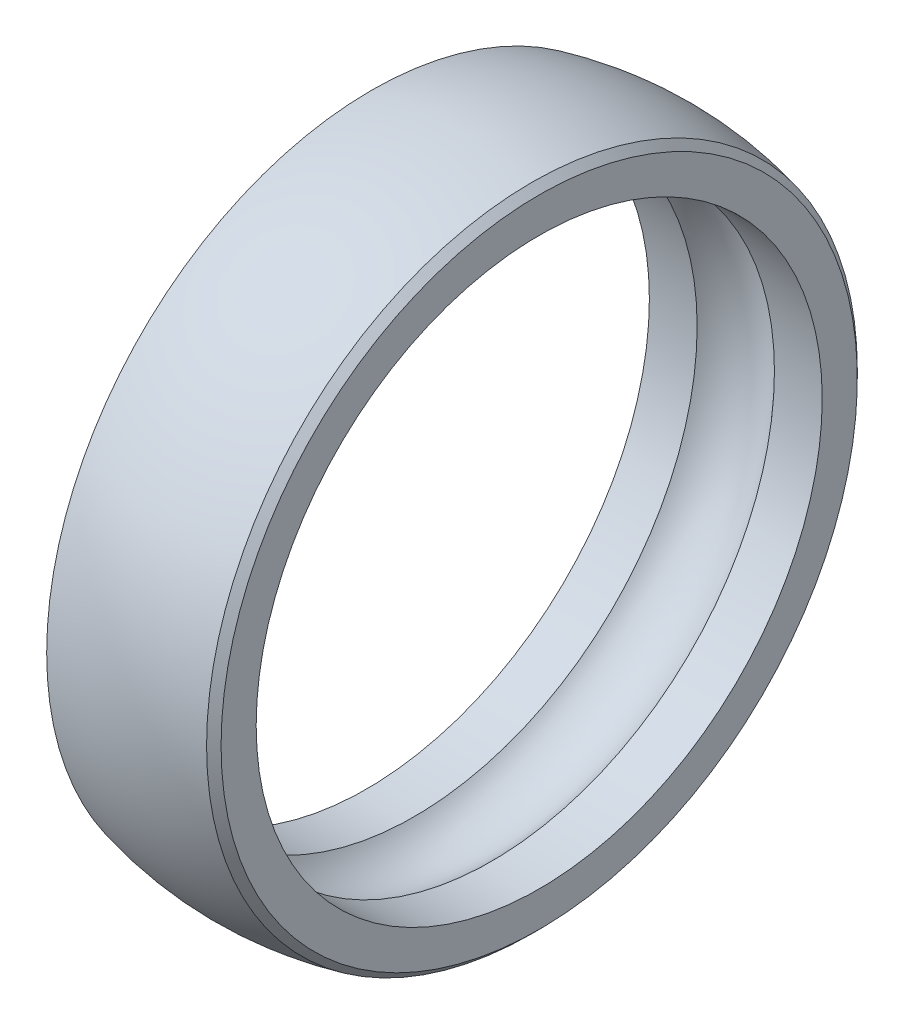
SolidWorks part; units mm, degrees
ref_plane "Plan1" through (0, 0, 0) normal (0, 0, 1) x (1, 0, 0)
ref_plane "Plan2" through (0, 0, 0) normal (0, 1, 0) x (1, 0, 0)
ref_plane "Plan3" through (0, 0, 0) normal (1, 0, 0) x (0, 0, -1)
ref_axis "Axe1" through (-50, 0, 0) along (1, 0, 0)
sketch "Esquisse1" plane through (0, 0, 0) normal (0, 1, 0) x (1, 0, 0)
  line L0 (0, 30) -> (0, 16) construction
  line L1 (16, 26.2) -> (0, 26.2) construction
  line L2 (16, 30) -> (16, 16) construction
  line L3 (1, 31) -> (15, 31) construction
  line L4 (0, 30) -> (0, 26.2)
  line L5 (16, 26.2) -> (11.5777, 26.2)
  line L6 (0, 0) -> (12, 0) construction
  line L7 (-50, 0) -> (200, 0) construction
  line L8 (16, 30) -> (16, 26.2)
  line L9 (1, 31) -> (15, 31)
  line L10 (4.4223, 26.2) -> (0, 26.2)
  arc A0 (1, 31) -> (0, 30) centre (1, 30) ccw construction
  circle A1 centre (8, 23) radius 4.8 construction
  arc A3 (16, 30) -> (15, 31) centre (15, 30) ccw construction
  arc A4 (1, 31) -> (0, 30) centre (1, 30) ccw
  arc A5 (11.5777, 26.2) -> (4.4223, 26.2) centre (8, 23) ccw
  arc A6 (16, 30) -> (15, 31) centre (15, 30) ccw
revolve "Base-Révolution" add sketch "Esquisse1" angle 360 about L6
sketch "Esquisse2" plane through (0, 0, 0) normal (0, 0, 1) x (1, 0, 0)
  line L0 (0, 0) -> (16, 0) construction
  line L1 (16, -30) -> (16, 30) construction
  line L2 (0, 29.95) -> (0, 39.5538)
  line L3 (0, 30) -> (0, -30) construction
  line L4 (0, 39.5538) -> (16, 39.5538)
  line L5 (16, 39.5538) -> (16, 29.95)
  arc A0 (16, 29.95) -> (0, 29.95) centre (8, 0) ccw
  dimension "D1" = 31
revolve "Enlèvement de matière-Révolution1" cut sketch "Esquisse2" angle 360 about L0
chamfer "Chanfrein1" distance 0.5 angle 45 2 edges at (16, -29.95, 0) (0, -29.95, 0) first distance on face at (16, 0, 26.2) first distance on face at (16, -29.95, 0)
